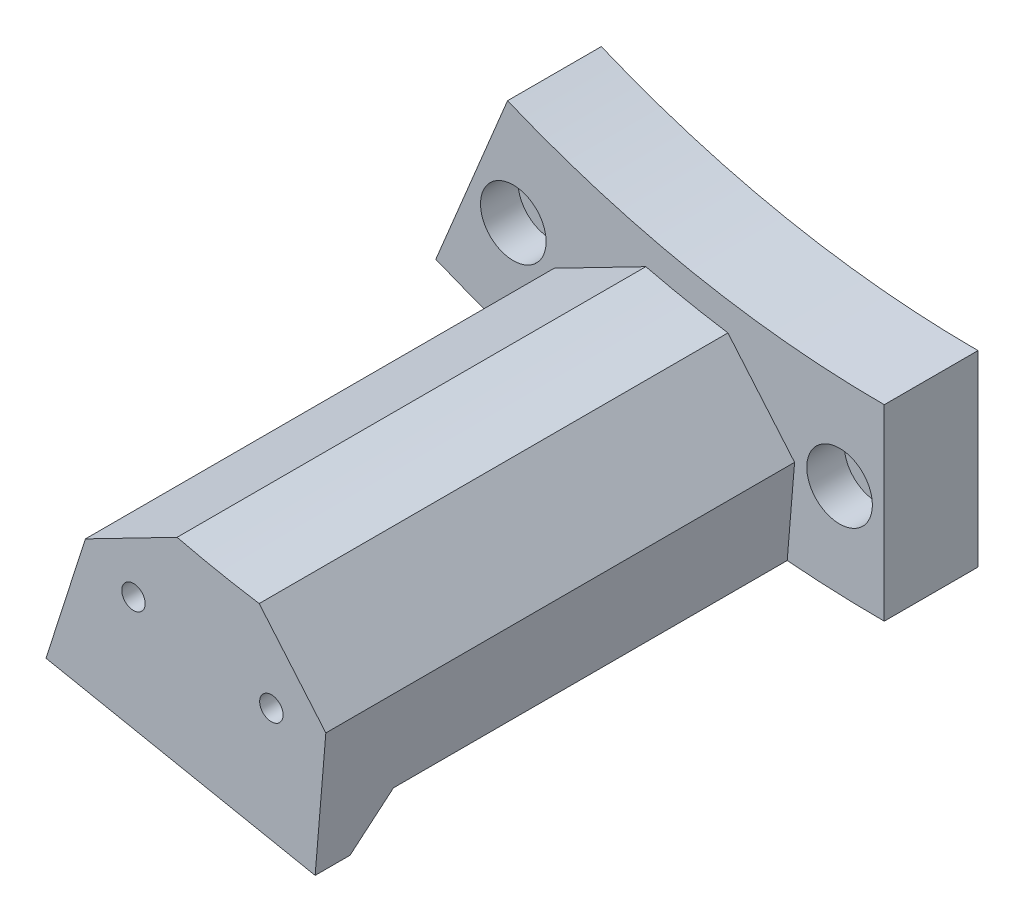
SolidWorks part; units mm, degrees
ref_plane "Plan de face" through (0, 0, 0) normal (0, 0, 1) x (1, 0, 0)
ref_plane "Plan de dessus" through (0, 0, 0) normal (0, 1, 0) x (1, 0, 0)
ref_plane "Plan de droite" through (0, 0, 0) normal (1, 0, 0) x (0, 0, -1)
sketch "Esquisse1" plane through (0, 0, 0) normal (0, 0, 1) x (1, 0, 0)
  line L0 (0, 0) -> (0, -125) construction
  line L1 (0, 0) -> (-47.8354, -115.4849) construction
  line L2 (-40.1818, -97.0074) -> (-47.8354, -115.4849)
  line L3 (0, -105) -> (0, -125)
  arc A0 (0, -125) -> (-47.8354, -115.4849) centre (0, 0) cw
  arc A1 (0, -105) -> (-40.1818, -97.0074) centre (0, 0) cw
  dimension "D2" = 125
  dimension "D3" = 105
  dimension "D1" = 22.5
extrude "Boss.-Extru.1" add sketch "Esquisse1" along normal blind 10
sketch "Esquisse2" plane through (0, 0, 10) normal (0, 0, 1) x (1, 0, 0)
  line L0 (0, 0) -> (-24.3863, -122.5982) construction
  line L1 (0, 0) -> (-10.351, -124.5707) construction
  line L2 (0, 0) -> (-38.108, -119.0495) construction
  line L3 (-32.9253, -102.8587) -> (-38.108, -119.0495)
  line L4 (-8.9433, -107.6291) -> (-10.351, -124.5707)
  arc A0 (-47.8354, -115.4849) -> (0, -125) centre (0, 0) ccw construction
  arc A1 (-10.351, -124.5707) -> (-38.108, -119.0495) centre (0, 0) cw
  arc A2 (-8.9433, -107.6291) -> (-32.9253, -102.8587) centre (0, 0) cw
  arc A3 (-40.1818, -97.0074) -> (0, -105) centre (0, 0) ccw construction
  point P10 (-24.3863, -122.5982)
  dimension "D1" = 3
  dimension "D2" = 13
extrude "Boss.-Extru.2" add sketch "Esquisse2" along normal blind 48
sketch "Esquisse4" plane through (0, 0, 58) normal (0, 0, 1) x (1, 0, 0)
  line L0 (-39.4132, -123.1267) -> (-10.7055, -128.837)
  line L1 (-10.7055, -128.837) -> (-8.9433, -107.6291)
  line L2 (-32.9253, -102.8587) -> (-39.4132, -123.1267)
  line L3 (-32.9253, -102.8587) -> (-38.108, -119.0495) construction
  line L4 (-10.351, -124.5707) -> (-8.9433, -107.6291) construction
  arc A0 (-32.9253, -102.8587) -> (-8.9433, -107.6291) centre (0, 0) ccw construction
  arc A1 (-32.9253, -102.8587) -> (-8.9433, -107.6291) centre (0, 0) ccw
  arc A2 (-38.108, -119.0495) -> (-10.351, -124.5707) centre (0, 0) ccw construction
  point P14 (-24.3863, -122.5982)
  dimension "D1" = 3.45
extrude "Boss.-Extru.3" add sketch "Esquisse4" along normal blind 2
chamfer "Chanfrein1" distance 6 angle 45 1 edges at (-24.3863, -122.5982, 58)
sketch "Esquisse5" plane through (0, 0, 10) normal (0, 0, 1) x (1, 0, 0)
  line L0 (0, 0) -> (-43.0087, -117.368) construction
  line L1 (0, 0) -> (-5.18, -124.8926) construction
  line L2 (-43.0087, -117.368) -> (-36.1273, -98.5891) construction
  line L3 (0, -125) -> (0, -105) construction
  line L4 (-40.1818, -97.0074) -> (-47.8354, -115.4849) construction
  arc A0 (-47.8354, -115.4849) -> (-38.108, -119.0495) centre (0, 0) ccw construction
  arc A1 (-10.351, -124.5707) -> (0, -125) centre (0, 0) ccw construction
  arc A2 (-40.1818, -97.0074) -> (0, -105) centre (0, 0) ccw construction
  arc A3 (0, -115) -> (-44.0086, -106.2461) centre (0, 0) cw construction
  circle A4 centre (-4.7656, -114.9012) radius 1.75
  circle A5 centre (-39.568, -107.9786) radius 1.75
  point P20 (-39.568, -107.9786)
  dimension "D1" = 3.5
extrude "Enlèv. mat.-Extru.1" cut sketch "Esquisse5" against normal up to next
sketch "Esquisse6" plane through (0, 0, 10) normal (0, 0, 1) x (1, 0, 0)
  circle A0 centre (-39.568, -107.9786) radius 3.5
  circle A1 centre (-4.7656, -114.9012) radius 3.5
  dimension "D1" = 7
extrude "Enlèv. mat.-Extru.2" cut sketch "Esquisse6" against normal blind 4
chamfer "Chanfrein2" distance 7.5 angle 45 2 edges at (-8.9433, -107.6291, 35) (-32.9253, -102.8587, 35)
sketch "Esquisse7" plane through (0, 0, 60) normal (0, 0, 1) x (1, 0, 0)
  line L0 (-21.0698, -105.9248) -> (-24.3863, -122.5982) construction
  line L1 (-30.0839, -112.7983) -> (-15.3721, -115.7247) construction
  arc A0 (-38.108, -119.0495) -> (-10.351, -124.5707) centre (0, 0) ccw construction
  arc A1 (-38.108, -119.0495) -> (-10.351, -124.5707) centre (0, 0) ccw construction
  arc A2 (-25.4295, -104.9635) -> (-16.674, -106.7051) centre (0, 0) ccw construction
  circle A3 centre (-30.0839, -112.7983) radius 1.25
  circle A4 centre (-15.3721, -115.7247) radius 1.25
  point P12 (-22.728, -114.2615)
  point P13 (-22.728, -114.2615)
  dimension "D1" = 2.5
  dimension "D2" = 15
extrude "Enlèv. mat.-Extru.3" cut sketch "Esquisse7" against normal blind 10
